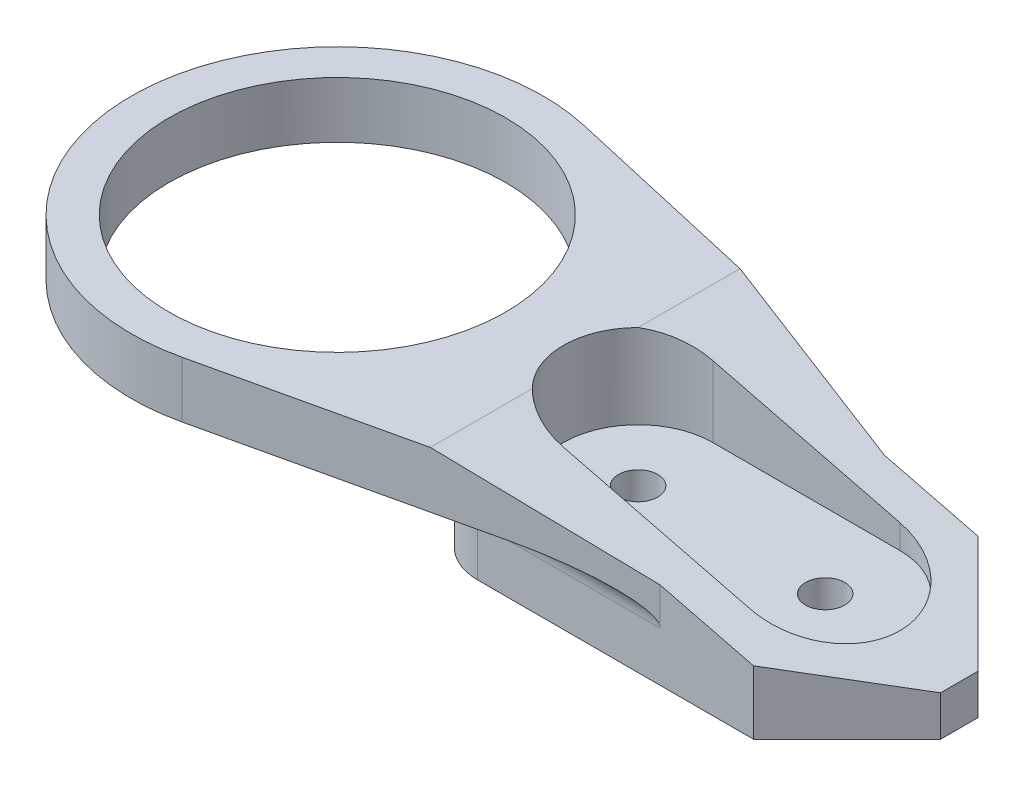
SolidWorks part; units mm, degrees
ref_plane "Front Plane" through (0, 0, 0) normal (0, 0, 1) x (1, 0, 0)
ref_plane "Top Plane" through (0, 0, 0) normal (0, 1, 0) x (1, 0, 0)
ref_plane "Right Plane" through (0, 0, 0) normal (1, 0, 0) x (0, 0, -1)
sketch "Sketch1" plane through (0, 0, 0) normal (0, 0, 1) x (1, 0, 0)
  line L0 (0, 0) -> (0, 7.15)
  line L1 (0, 7.15) -> (25, 7.15)
  line L2 (25, 7.15) -> (25, 0)
  line L3 (25, 0) -> (0, 0)
extrude "Boss-Extrude1" add sketch "Sketch1" along normal blind 12
sketch "Sketch2" plane through (0, 7.15, 0) normal (0, 1, 0) x (1, 0, 0)
  line L0 (0, -6) -> (-8.25, -6) construction
  line L1 (0, -12) -> (0, 0) construction
  line L3 (25, 0) -> (0, 0) construction
  line L5 (25, -12) -> (0, -12) construction
  line L8 (15, -6) -> (15, 0)
  line L11 (15, 0) -> (-5.8049, 4.7375)
  line L12 (15, -6) -> (15, -12)
  line L13 (15, -12) -> (-5.8049, -16.7375)
  arc A6 (-5.8049, 4.7375) -> (-5.8049, -16.7375) centre (-8.25, -6) ccw
  line M4 (25, 0) -> (0, 0)
  line M5 (0, 0) -> (0, -12)
  line M6 (0, -12) -> (25, -12)
extrude "Boss-Extrude2" add sketch "Sketch2" against normal blind 3 contours M6 M5 M4 region at (-7.1054, 7.15, 6)
sketch "Sketch3" plane through (0, 4.15, 0) normal (0, -1, 0) x (1, 0, 0)
  line L0 (-8.25, 6) -> (2.25, 6) construction
  line L1 (2.25, 6) -> (2.25, 12)
  line L2 (0, 12) -> (25, 12) construction
  line L3 (2.25, 12) -> (0, 12)
  line L4 (0, 12) -> (0, 0)
  line L5 (0, 0) -> (2.25, 0)
  line L6 (15, 0) -> (0, 0) construction
  line L7 (2.25, 0) -> (2.25, 6)
  circle A0 centre (-8.25, 6) radius 11.0124 construction
extrude "Cut-Extrude1" cut sketch "Sketch3" along normal blind 21
sketch "Sketch4" plane through (0, 4.15, 0) normal (0, -1, 0) x (1, 0, 0)
  circle A2 centre (-8.25, 6) radius 9
extrude "Cut-Extrude2" cut sketch "Sketch4" against normal blind 10
chamfer "Chamfer1" distance 5 distance2 20 1 edges at (25, 7.15, 6) first distance on face at (25, 3.575, 6)
chamfer "Chamfer2" distance 5 angle 45 2 edges at (25, 1.075, 12) (25, 1.075, 0)
sketch "Sketch6" plane through (0, 7.15, 0) normal (0, 1, 0) x (1, 0, 0)
  line L0 (-0.0037, -6) -> (7.8299, -6) construction
  line L1 (7.8299, -6) -> (17.8299, -6) construction
  circle A0 centre (-8.5537, -6) radius 8.55 construction
  circle A1 centre (7.8299, -6) radius 1.05
  circle A2 centre (17.8299, -6) radius 1.05
  dimension "D1" = 10
extrude "Cut-Extrude3" cut sketch "Sketch6" against normal blind 10
sketch "Sketch7" plane through (0, 7.15, 0) normal (0, 1, 0) x (1, 0, 0)
  line L0 (7.8299, -2) -> (17.8299, -2)
  line L1 (17.8299, -10) -> (7.8299, -10)
  arc A0 (7.8299, -2) -> (7.8299, -10) centre (7.8299, -6) ccw
  arc A1 (17.8299, -10) -> (17.8299, -2) centre (17.8299, -6) ccw
extrude "Cut-Extrude4" cut sketch "Sketch7" against normal blind 4.5
fillet "Fillet1" radius 3 2 edges at (2.25, 2.075, 12) (2.25, 2.075, 0)
fillet "Fillet2" radius 1.5 5 edges at (10.125, 4.15, 12) (3.1287, 4.15, 11.1213) (2.25, 4.15, 6) (3.1287, 4.15, 0.8787) (10.125, 4.15, 0)
